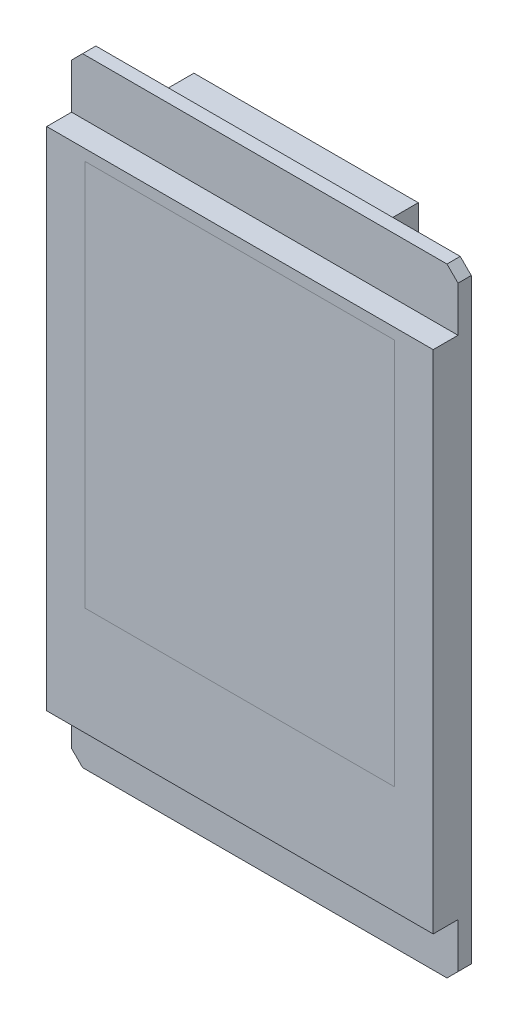
SolidWorks part; units mm, degrees
ref_plane "前视基准面" through (0, 0, 0) normal (0, 0, 1) x (1, 0, 0)
ref_plane "上视基准面" through (0, 0, 0) normal (0, 1, 0) x (1, 0, 0)
ref_plane "右视基准面" through (0, 0, 0) normal (1, 0, 0) x (0, 0, -1)
other "Configuration Table"
sketch "草图1" plane through (0, 0, 0) normal (0, 0, 1) x (1, 0, 0)
  line L0 (0, 55) -> (1, 56)
  line L1 (1, 0) -> (34, 0)
  line L2 (0, 1) -> (0, 55)
  line L3 (1, 56) -> (34, 56)
  line L4 (35, 1) -> (35, 55)
  line L5 (34, 56) -> (35, 55)
  line L6 (34, 0) -> (35, 1)
  line L7 (0, 1) -> (1, 0)
  point P0 (0, 0)
  point P1 (35, 56)
  point P2 (0, 56)
  point P3 (35, 0)
  dimension "D1" = 56
  dimension "D2" = 35
extrude "凸台-拉伸1" add sketch "草图1" along normal blind 1.2
sketch "草图2" plane through (0, 0, 1.2) normal (0, 0, 1) x (1, 0, 0)
  line L0 (0, 55) -> (0, 1) construction
  line L1 (0, 5.08) -> (35, 5.08)
  line L2 (0, 5.08) -> (0, 50.91)
  line L3 (0, 50.91) -> (35, 50.91)
  line L4 (35, 5.08) -> (35, 50.91)
  line L5 (35, 1) -> (35, 55) construction
  line L6 (34, 56) -> (1, 56) construction
  point P8 (0, 51.7335)
  dimension "D1" = 45.83
  dimension "D2" = 5.09
extrude "凸台-拉伸2" add sketch "草图2" along normal blind 2.25
sketch "草图3" plane through (0, 0, 3.45) normal (0, 0, 1) x (1, 0, 0)
  line L0 (17.5, 49.91) -> (17.5, 51.91) construction
  line L1 (3.485, 14.87) -> (31.515, 14.87)
  line L2 (3.485, 14.87) -> (3.485, 49.91)
  line L3 (3.485, 49.91) -> (31.515, 49.91)
  line L4 (31.515, 14.87) -> (31.515, 49.91)
  line L5 (35, 50.91) -> (0, 50.91) construction
  line L6 (35, 50.91) -> (0, 50.91) construction
  point P8 (17.5, 50.91)
  point P9 (17.5, 50.91)
  dimension "D1" = 35.04
  dimension "D2" = 28.03
  dimension "D3" = 1
wrap "包覆1" sketch "草图3" wrap type scribe source sketch "草图3"
sketch "草图4" plane through (0, 0, 0) normal (0, 0, -1) x (-1, 0, 0)
  line L0 (-17.5, 55.77) -> (-17.5, 53.23) construction
  line L1 (-27.66, 53.23) -> (-7.34, 53.23)
  line L2 (-27.66, 53.23) -> (-27.66, 55.77)
  line L3 (-27.66, 55.77) -> (-7.34, 55.77)
  line L4 (-7.34, 53.23) -> (-7.34, 55.77)
  line L5 (-34, 56) -> (-1, 56) construction
  point P8 (-17.5, 56)
  dimension "D1" = 20.32
  dimension "D2" = 2.54
  dimension "D3" = 0.23
extrude "凸台-拉伸3" add sketch "草图4" along normal blind 2.54
